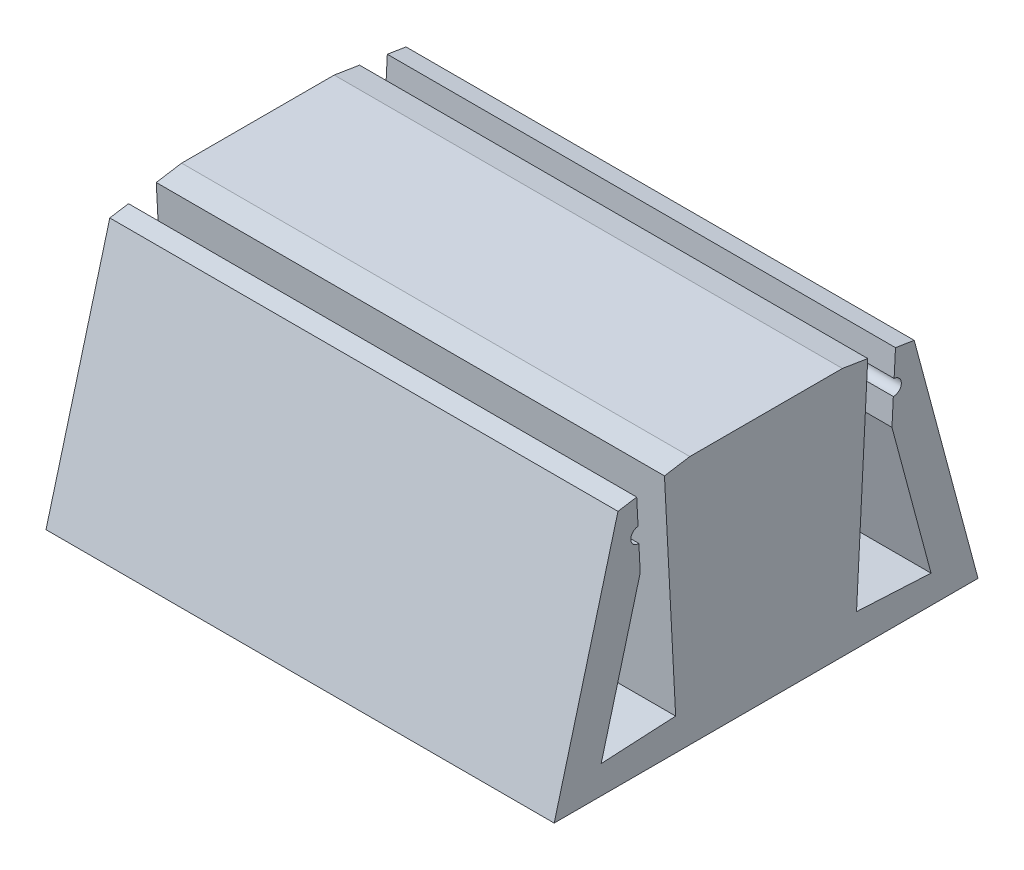
SolidWorks part; units mm, degrees
ref_plane "Front Plane" through (0, 0, 0) normal (0, 0, 1) x (1, 0, 0)
ref_plane "Top Plane" through (0, 0, 0) normal (0, 1, 0) x (1, 0, 0)
ref_plane "Right Plane" through (0, 0, 0) normal (1, 0, 0) x (0, 0, -1)
sketch "Sketch1" plane through (0, 0, 0) normal (1, 0, 0) x (0, 0, -1)
  line L0 (3.6311, 0.3059) -> (9.4677, 0) construction
  line L1 (3.904, 5.5131) -> (4.9077, 5.4605) construction
  line L2 (6.2203, 9.4885) -> (6.0816, 6.8415) construction
  line L3 (6.0816, 6.8415) -> (7.6191, 1.1033)
  line L4 (7.6191, 1.1033) -> (4.6874, 1.2569)
  line L5 (4.6874, 1.2569) -> (5.128, 9.664)
  line L6 (5.128, 9.664) -> (4.13, 9.8243)
  line L7 (4.13, 9.8243) -> (3.6311, 0.3059) construction
  line L8 (6.2203, 9.4885) -> (6.1666, 8.4646)
  line L9 (6.1352, 7.8654) -> (6.0816, 6.8415)
  line L10 (6.2203, 9.4885) -> (6.9569, 9.3702)
  line L11 (6.9569, 9.3702) -> (9.4677, 0)
  line L12 (6.1532, 1.1801) -> (6.1006, 0.1765) construction
  line L13 (1.128, 0) -> (1.128, 7.6812) construction
  line L14 (-3.8973, 1.1801) -> (-3.8447, 0.1765) construction
  line L15 (-5.3632, 1.1033) -> (-2.4314, 1.2569)
  line L16 (-3.9644, 9.4885) -> (-3.8256, 6.8415) construction
  line L17 (-1.6481, 5.5131) -> (-2.6517, 5.4605) construction
  line L18 (-1.3752, 0.3059) -> (-7.2117, 0) construction
  line L19 (-4.701, 9.3702) -> (-7.2117, 0)
  line L20 (-3.9644, 9.4885) -> (-4.701, 9.3702)
  line L21 (-3.8793, 7.8654) -> (-3.8256, 6.8415)
  line L22 (-3.9644, 9.4885) -> (-3.9107, 8.4646)
  line L23 (-1.874, 9.8243) -> (-1.3752, 0.3059) construction
  line L24 (-2.872, 9.664) -> (-1.874, 9.8243)
  line L25 (-2.4314, 1.2569) -> (-2.872, 9.664)
  line L26 (-3.8256, 6.8415) -> (-5.3632, 1.1033)
  line L27 (-1.874, 9.8243) -> (4.13, 9.8243)
  line L28 (-7.2117, 0) -> (9.4677, 0)
  arc A0 (6.1666, 8.4646) -> (6.1352, 7.8654) centre (6.1509, 8.165) cw
  arc A1 (-3.9107, 8.4646) -> (-3.8793, 7.8654) centre (-3.895, 8.165) ccw
  dimension "D1" = 0.3
  dimension "D2" = 1.1
  dimension "D3" = 72
  dimension "D4" = 1.5
  dimension "D5" = 8
extrude "Boss-Extrude1" add sketch "Sketch1" along normal mid plane 20 contours L8 A0 L9 L3 L4 L5 L6 L27 L24 L25 L15 L26 L21 A1 L22 L20 L19 L28 L11 L10
